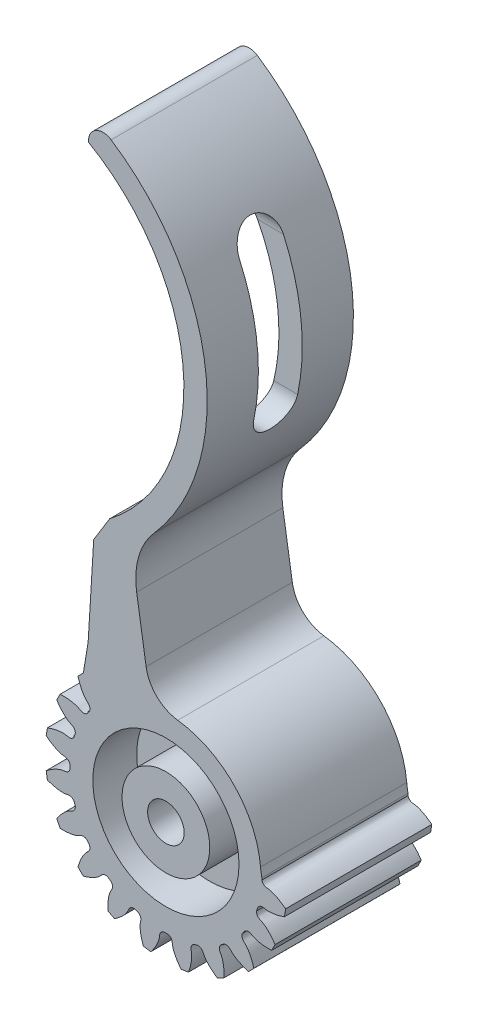
SolidWorks part; units mm, degrees
material "聚脂树脂"
ref_plane "前视基准面" through (0, 0, 0) normal (0, 0, 1) x (1, 0, 0)
ref_plane "上视基准面" through (0, 0, 0) normal (0, 1, 0) x (1, 0, 0)
ref_plane "右视基准面" through (0, 0, 0) normal (1, 0, 0) x (0, 0, -1)
other "Configuration Table"
sketch "草图1" plane through (0, 0, 0) normal (0, 0, 1) x (1, 0, 0)
  circle A0 centre (0, 0) radius 16.5
extrude "凸台-拉伸1" add sketch "草图1" along normal blind 20
ref_axis "基准轴1" through (0, 0, -1.5) along (0, 0, 1)
sketch "草图2" plane through (0, 0, 0) normal (0, 0, 1) x (1, 0, 0)
  line L0 (0, 0) -> (0, 16.5) construction
  circle A0 centre (0, 0) radius 16.5 construction
  arc A1 (0.29, 13.1218) -> (-0.29, 13.1218) centre (0, 0) ccw
  arc A2 (4.7717, 18.7474) -> (-4.7717, 18.7474) centre (0, 0) ccw
  spline S0 degree 3 poles (0.29, 13.1218) (0.9168, 13.3402) (0.8356, 13.7807) (0.9193, 14.205) (0.9283, 14.2463) (0.9395, 14.293) (0.9529, 14.3448) (0.969, 14.4018) (0.9878, 14.4638) (1.0095, 14.5309) (1.0345, 14.6028) (1.0629, 14.6795) (1.0948, 14.7608) (1.1305, 14.8467) (1.1702, 14.9371) (1.2141, 15.0317) (1.2623, 15.1305) (1.315, 15.2334) (1.3725, 15.3401) (1.4349, 15.4506) (1.5023, 15.5646) (1.575, 15.6821) (1.653, 15.8029) (1.7366, 15.9267) (1.826, 16.0534) (1.9211, 16.1829) (2.0223, 16.3149) (2.1296, 16.4493) (2.2432, 16.5859) (2.3632, 16.7244) (2.4897, 16.8646) (2.6229, 17.0065) (2.7628, 17.1496) (2.9095, 17.2939) (3.0632, 17.4391) (3.224, 17.585) (3.3918, 17.7313) (3.567, 17.8779) (3.7493, 18.0245) (3.9391, 18.1709) (4.1363, 18.3167) (4.4122, 18.5125) (4.6259, 18.6545) (4.7717, 18.7474) knots 0 0 0 0 0.165916 0.170906 0.176664 0.183189 0.190482 0.198542 0.207371 0.216967 0.22733 0.238462 0.250361 0.263027 0.276462 0.290664 0.305634 0.321371 0.337876 0.355149 0.37319 0.391998 0.411574 0.431917 0.453028 0.474907 0.497554 0.520968 0.54515 0.570099 0.595817 0.622302 0.649554 0.677575 0.706363 0.735918 0.766242 0.797333 0.829191 0.861818 0.895212 0.929373 1 1 1 1
  spline S1 degree 3 poles (-0.29, 13.1218) (-0.9168, 13.3402) (-0.8356, 13.7807) (-0.9193, 14.205) (-0.9283, 14.2463) (-0.9395, 14.293) (-0.9529, 14.3448) (-0.969, 14.4018) (-0.9878, 14.4638) (-1.0095, 14.5309) (-1.0345, 14.6028) (-1.0629, 14.6795) (-1.0948, 14.7608) (-1.1305, 14.8467) (-1.1702, 14.9371) (-1.2141, 15.0317) (-1.2623, 15.1305) (-1.315, 15.2334) (-1.3725, 15.3401) (-1.4349, 15.4506) (-1.5023, 15.5646) (-1.575, 15.6821) (-1.653, 15.8029) (-1.7366, 15.9267) (-1.826, 16.0534) (-1.9211, 16.1829) (-2.0223, 16.3149) (-2.1296, 16.4493) (-2.2432, 16.5859) (-2.3632, 16.7244) (-2.4897, 16.8646) (-2.6229, 17.0065) (-2.7628, 17.1496) (-2.9095, 17.2939) (-3.0632, 17.4391) (-3.224, 17.585) (-3.3918, 17.7313) (-3.567, 17.8779) (-3.7493, 18.0245) (-3.9391, 18.1709) (-4.1363, 18.3167) (-4.4122, 18.5125) (-4.6259, 18.6545) (-4.7717, 18.7474) knots 0 0 0 0 0.165916 0.170906 0.176664 0.183189 0.190482 0.198542 0.207371 0.216967 0.22733 0.238462 0.250361 0.263027 0.276462 0.290664 0.305634 0.321371 0.337876 0.355149 0.37319 0.391998 0.411574 0.431917 0.453028 0.474907 0.497554 0.520968 0.54515 0.570099 0.595817 0.622302 0.649554 0.677575 0.706363 0.735918 0.766242 0.797333 0.829191 0.861818 0.895212 0.929373 1 1 1 1
extrude "切除-拉伸1" cut sketch "草图2" along normal through all
pattern_circular "阵列(圆周)1" count 20 over 360 about axis through (0, 0, -1.5) along (0, 0, 1) of "切除-拉伸1"
sketch "草图3" plane through (0, 0, 0) normal (0, 0, 1) x (1, 0, 0)
  circle A0 centre (0, 0) radius 15 construction
  dimension "Dn" = 30
sketch "草图4" plane through (0, 0, 20) normal (0, 0, 1) x (1, 0, 0)
  line L0 (0, 0) -> (0, 24.252) construction
  line L1 (0, 0) -> (-4.1504, 26.2048) construction
  line L2 (-14.6667, -3.2847) -> (-22.6322, 47.0071) construction
  line L3 (-12.7072, 29.0903) -> (-7.9015, -1.2515)
  line L4 (-4.8057, 30.3418) -> (0, 0)
  line L5 (-11.2693, 79.2123) -> (-10.5853, 75.2708)
  line L6 (-11.294, 12.029) -> (-10.6385, 16.029)
  line L7 (-3.0932, 16.2075) -> (-2.5812, 16.2969)
  line L8 (0, 0) -> (-34.8237, -5.5155) construction
  line L9 (-7.9015, -1.2515) -> (0, 0)
  circle A0 centre (0, 0) radius 12.5 construction
  circle A1 centre (-23.5381, 52.727) radius 29.189 construction
  arc A2 (-2.0665, 16.3701) -> (-3.0932, 16.2075) centre (0, 0) ccw construction
  arc A3 (-4.8057, 30.3418) -> (-11.2693, 79.2123) centre (-23.5381, 52.727) ccw
  circle A4 centre (-23.5381, 52.727) radius 26 construction
  arc A6 (-12.7072, 29.0903) -> (-10.5853, 75.2708) centre (-23.5381, 52.727) ccw
  arc A8 (-3.7791, 12.5692) -> (-4.3306, 12.39) centre (0, 0) ccw construction
  arc A9 (-7.024, 14.9303) -> (-7.9502, 14.4584) centre (0, 0) ccw construction
  arc A10 (-7.4782, 10.7862) -> (-7.9474, 10.4453) centre (0, 0) ccw construction
  arc A12 (-3.7791, 12.5692) -> (-4.3306, 12.39) centre (0, 0) ccw
  arc A13 (-7.024, 14.9303) -> (-7.9502, 14.4584) centre (0, 0) ccw
  arc A14 (-7.4782, 10.7862) -> (-7.9474, 10.4453) centre (0, 0) ccw
  spline S0 degree 3 poles (2295.3671, 1929.7263) (-117.6975, -134.774) (-40.8912, 20.8175) (-11.0168, 11.9483) (-10.7713, 11.8675) (-10.4966, 11.7648) (-10.2471, 11.6599) (-10.0224, 11.5547) (-9.822, 11.4509) (-9.671, 11.3649) (-9.5386, 11.2841) (-9.4441, 11.2225) (-9.3578, 11.1623) (-9.3008, 11.1209) (-9.2491, 11.0817) (-9.2026, 11.0451) (-9.1503, 11.0021) (-9.105, 10.9626) (-4.5559, 6.7443) (-24.7562, -23.4769) (1867.2073, 2351.7135) knots -12.160638 -12.160638 -12.160638 -12.160638 0.502446 0.525093 0.568083 0.608002 0.644851 0.678629 0.709336 0.736973 0.749639 0.77267 0.783033 0.792629 0.801458 0.809518 0.816811 0.829094 0.834084 3.350793 3.350793 3.350793 3.350793 only from (-11.294, 12.029) to (-7.9474, 10.4453) construction
  spline S1 degree 3 poles (-3000.2151, -128.3054) (33.5455, 6.2288) (-2.7783, 7.6499) (-3.5171, 13.8097) (-3.5224, 13.8696) (-3.5265, 13.9372) (-3.5289, 13.9963) (-3.5307, 14.0865) (-3.5293, 14.2134) (-3.5206, 14.3824) (-3.5033, 14.5733) (-3.4754, 14.7858) (-3.4352, 15.0192) (-3.381, 15.2729) (-3.3111, 15.5461) (-3.2398, 15.7847) (-3.1737, 15.9845) (7.1936, 45.3178) (178.2143, 16.0013) (-2910.3372, -722.7198) knots -2.350827 -2.350827 -2.350827 -2.350827 0.165916 0.170906 0.183189 0.190482 0.198542 0.207371 0.22733 0.250361 0.276462 0.305634 0.337876 0.37319 0.411574 0.453028 0.474907 0.497554 13.160601 13.160601 13.160601 13.160601 only from (-3.7791, 12.5692) to (-3.0932, 16.2075) construction
  spline S2 degree 3 poles (2779.3421, 1125.9713) (-153.5845, -91.8071) (-32.4569, 32.4347) (-6.7853, 14.7679) (-6.5768, 14.6152) (-6.3474, 14.4326) (-6.1425, 14.2557) (-5.9612, 14.0862) (-5.8028, 13.9257) (-5.6857, 13.7971) (-5.5848, 13.6794) (-5.514, 13.5916) (-5.4504, 13.5077) (-5.409, 13.4507) (-5.3719, 13.3975) (-5.3391, 13.3482) (-5.3027, 13.2912) (-5.2717, 13.2396) (-2.2488, 7.822) (-30.7993, -14.6778) (2502.5391, 1659.6136) knots -12.160638 -12.160638 -12.160638 -12.160638 0.502446 0.525093 0.568083 0.608002 0.644851 0.678629 0.709336 0.736973 0.749639 0.77267 0.783033 0.792629 0.801458 0.809518 0.816811 0.829094 0.834084 3.350793 3.350793 3.350793 3.350793 only from (-7.024, 14.9303) to (-4.3306, 12.39) construction
  spline S3 degree 3 poles (-2813.7256, -1049.1431) (29.9789, 16.29) (-5.0063, 6.4169) (-7.6124, 12.047) (-7.636, 12.1023) (-7.6607, 12.1653) (-7.6812, 12.2208) (-7.7108, 12.3061) (-7.7487, 12.4272) (-7.7927, 12.5905) (-7.8352, 12.7775) (-7.8743, 12.9882) (-7.9082, 13.2226) (-7.9351, 13.4806) (-7.9531, 13.762) (-7.959, 14.011) (-7.9578, 14.2215) (-7.1625, 45.3227) (164.5472, 70.2894) (-2544.5625, -1586.6911) knots -2.350827 -2.350827 -2.350827 -2.350827 0.165916 0.170906 0.183189 0.190482 0.198542 0.207371 0.22733 0.250361 0.276462 0.305634 0.337876 0.37319 0.411574 0.453028 0.474907 0.497554 13.160601 13.160601 13.160601 13.160601 only from (-7.4782, 10.7862) to (-7.9502, 14.4584) construction
  spline S4 degree 3 poles (-3.7791, 12.5692) (-3.2504, 12.9706) (-3.4637, 13.3644) (-3.5171, 13.8097) (-3.5224, 13.8696) (-3.5265, 13.9372) (-3.5289, 13.9963) (-3.5307, 14.0865) (-3.5293, 14.2134) (-3.5206, 14.3824) (-3.5033, 14.5733) (-3.4754, 14.7858) (-3.4352, 15.0192) (-3.381, 15.2729) (-3.3111, 15.5461) (-3.224, 15.8378) (-3.1479, 16.0599) (-3.1017, 16.1848) (-3.0932, 16.2075) knots 0 0 0 0 0.165916 0.170906 0.183189 0.190482 0.198542 0.207371 0.22733 0.250361 0.276462 0.305634 0.337876 0.37319 0.411574 0.453028 0.497554 0.507432 0.507432 0.507432 0.507432
  spline S5 degree 3 poles (-7.024, 14.9303) (-6.9129, 14.8568) (-6.7202, 14.7228) (-6.459, 14.5233) (-6.2419, 14.3433) (-6.0489, 14.1699) (-5.8792, 14.0047) (-5.7318, 13.8492) (-5.6234, 13.7255) (-5.5309, 13.613) (-5.4664, 13.5298) (-5.409, 13.4507) (-5.3719, 13.3975) (-5.3391, 13.3482) (-5.3027, 13.2912) (-5.2717, 13.2396) (-5.0532, 12.848) (-4.9943, 12.404) (-4.3306, 12.39) knots 0.492568 0.492568 0.492568 0.492568 0.546972 0.588426 0.62681 0.662124 0.694366 0.723538 0.749639 0.761538 0.783033 0.792629 0.801458 0.809518 0.816811 0.829094 0.834084 1 1 1 1
  spline S6 degree 3 poles (-7.4782, 10.7862) (-7.0995, 11.3313) (-7.424, 11.64) (-7.6124, 12.047) (-7.636, 12.1023) (-7.6607, 12.1653) (-7.6812, 12.2208) (-7.7108, 12.3061) (-7.7487, 12.4272) (-7.7927, 12.5905) (-7.8352, 12.7775) (-7.8743, 12.9882) (-7.9082, 13.2226) (-7.9351, 13.4806) (-7.9531, 13.762) (-7.9603, 14.0664) (-7.9566, 14.3011) (-7.9513, 14.4342) (-7.9502, 14.4584) knots 0 0 0 0 0.165916 0.170906 0.183189 0.190482 0.198542 0.207371 0.22733 0.250361 0.276462 0.305634 0.337876 0.37319 0.411574 0.453028 0.497554 0.507432 0.507432 0.507432 0.507432
  spline S7 degree 3 poles (-11.294, 12.029) (-11.1656, 11.9934) (-10.9409, 11.9255) (-10.6308, 11.8165) (-10.3687, 11.7125) (-10.1316, 11.6072) (-9.9192, 11.5025) (-9.7309, 11.4002) (-9.5896, 11.316) (-9.4669, 11.2376) (-9.3798, 11.1783) (-9.3008, 11.1209) (-9.2491, 11.0817) (-9.2026, 11.0451) (-9.1503, 11.0021) (-9.105, 10.9626) (-8.7761, 10.6576) (-8.5829, 10.2536) (-7.9474, 10.4453) knots 0.492568 0.492568 0.492568 0.492568 0.546972 0.588426 0.62681 0.662124 0.694366 0.723538 0.749639 0.761538 0.783033 0.792629 0.801458 0.809518 0.816811 0.829094 0.834084 1 1 1 1
  dimension "D6" = 52
  dimension "D7" = 76
  dimension "D5" = 30.72
  dimension "D10" = 25
  dimension "D9" = 80
  dimension "D1" = 9
  dimension "D2" = 15
  dimension "D3" = 8
  dimension "D4" = 30.72
  dimension "D8" = 4
extrude "凸台-拉伸2" add sketch "草图4" against normal blind 20 contours S7 A14 S6 A13 S5 A12 S4 L7 A6 | S7 region at (3.146, 51.5009, 20) region at (-10.6183, 13.2048, 20)
fillet "圆角1" radius 1 1 edges
fillet "圆角2" radius 2 1 edges at (-11.2693, 79.2123, 10)
fillet "圆角4" radius 10 1 edges at (-4.8057, 30.3418, 10)
sketch "草图5" plane through (0, 0, 20) normal (0, 0, 1) x (1, 0, 0)
  circle A0 centre (0, 0) radius 2.5
  dimension "D1" = 5
extrude "切除-拉伸2" cut sketch "草图5" against normal blind 20
chamfer "倒角1" distance 5 angle 45 1 edges at (-12.7072, 29.0903, 10) first distance on face at (-11.6728, 22.5596, 10)
sketch "草图7" plane through (0, 0, 0) normal (0, 0, -1) x (-1, 0, 0)
  circle A0 centre (0, 0) radius 10
  dimension "D1" = 20
extrude "切除-拉伸3" cut sketch "草图7" against normal blind 3
sketch "草图8" plane through (0, 0, 20) normal (0, 0, 1) x (1, 0, 0)
  circle A0 centre (0, 0) radius 6
  circle A1 centre (0, 0) radius 10
  dimension "D1" = 12
  dimension "D2" = 20
extrude "切除-拉伸4" cut sketch "草图8" against normal blind 6
sketch "草图9" plane through (0, 0, 0) normal (1, 0, 0) x (0, 0, -1)
  line L0 (-10, 46.7) -> (-10, 64.7) construction
  line L5 (-13, 46.7) -> (-13, 64.7)
  line L6 (-7, 46.7) -> (-7, 64.7)
  line L7 (0, 33.4384) -> (0, 77.1105) construction
  arc A0 (-13, 46.7) -> (-7, 46.7) centre (-10, 46.7) ccw
  arc A1 (-7, 64.7) -> (-13, 64.7) centre (-10, 64.7) ccw
  point P2 (-10, 55.7)
  dimension "D2" = 3
  dimension "D1" = 18
  dimension "D3" = 10
  dimension "D4" = 55.7
extrude "切除-拉伸5" cut sketch "草图9" along normal blind 10 and the other way blind 10
sketch "草图10" plane through (0, 0, 20) normal (0, 0, 1) x (1, 0, 0)
  line L0 (0, 0) -> (23.832, 0)
  line L1 (0, 0) -> (0, 19.24)
  line L2 (0, 19.24) -> (23.832, 19.24)
  line L3 (23.832, 19.24) -> (23.832, 0)
  line L4 (-2.7171, 17.1551) -> (0, 0)
  line L5 (0, 19.24) -> (-2.7171, 17.1551)
  line L6 (-9.8737, 28.5687) -> (-10.6385, 16.029)
  line L7 (-7.6851, 32.1191) -> (-12.0622, 25.0182) construction
  line L8 (-10.6385, 16.029) -> (-12.0622, 25.0182)
  line L9 (-12.0622, 25.0182) -> (-9.8737, 28.5687)
  circle A0 centre (0, 0) radius 13
  dimension "D1" = 26
extrude "切除-拉伸6" cut sketch "草图10" against normal blind 31 contours A0 L0 L3 L2 L1 | A0 L1 L5 L4 | L9 L8 L6 region at (14.5229, 11.2914, 20) region at (-1.1393, 15.7433, 20) region at (-10.8581, 23.2053, 20)
fillet "圆角5" radius 10 1 edges at (13, 0, 10)
sketch "草图11" plane through (0, 0, 3) normal (0, 0, -1) x (-1, 0, 0)
  circle A0 centre (0, 0) radius 6.5
  circle A1 centre (0, 0) radius 10
  dimension "D1" = 13
  dimension "D2" = 20
extrude "切除-拉伸7" cut sketch "草图11" against normal blind 3
sketch "草图12" plane through (0, 0, 6) normal (0, 0, -1) x (-1, 0, 0)
  circle A0 centre (0, 0) radius 7.5
  circle A1 centre (0, 0) radius 6.5
  dimension "D1" = 15
  dimension "D2" = 13
extrude "凸台-拉伸3" add sketch "草图12" along normal blind 6
fillet "圆角6" radius 5 1 edges at (-2.0336, 12.8399, 10)
